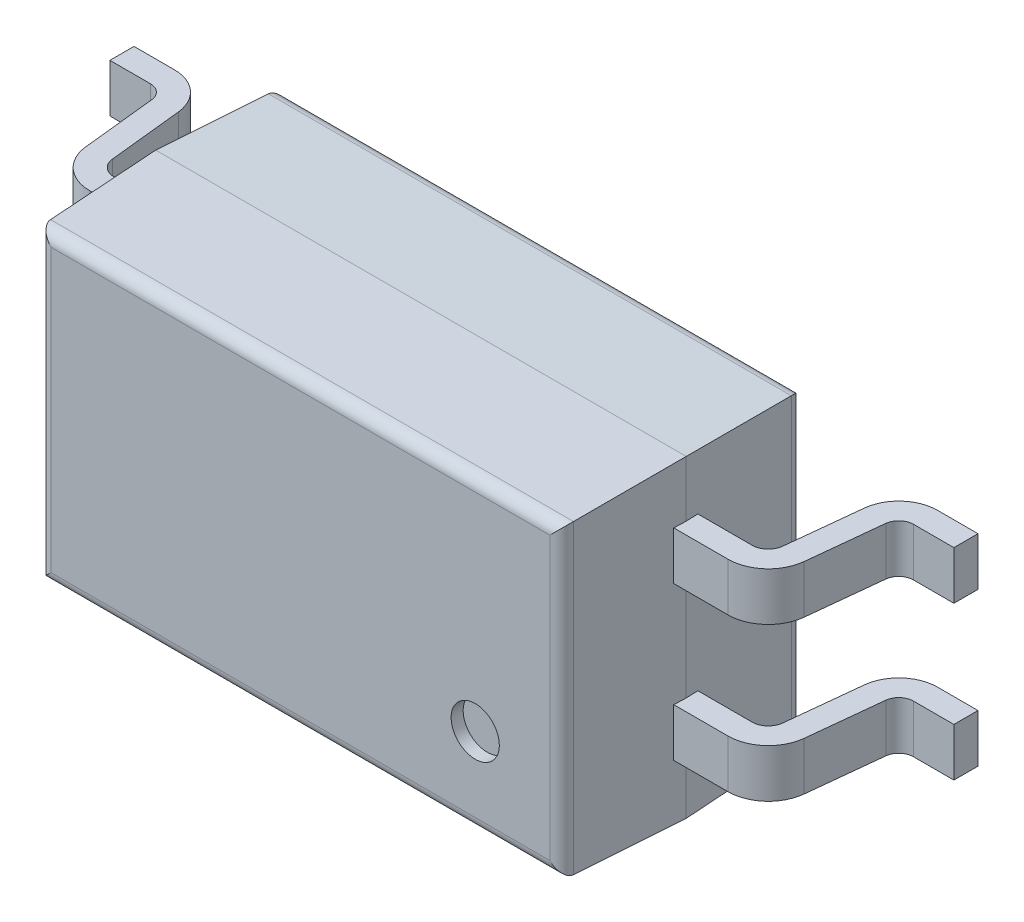
SolidWorks part; units mm, degrees
ref_plane "Plan de face" through (0, 0, 0) normal (0, 0, 1) x (1, 0, 0)
ref_plane "Plan de dessus" through (0, 0, 0) normal (0, 1, 0) x (1, 0, 0)
ref_plane "Plan de droite" through (0, 0, 0) normal (1, 0, 0) x (0, 0, -1)
sketch "Esquisse1" plane through (0, 0, 0) normal (0, 0, 1) x (1, 0, 0)
  line L1 (4.4, 2.6) -> (0, 2.6)
  line L2 (4.4, 2.6) -> (4.4, 0)
  line L3 (4.4, 0) -> (0, 0)
  line L4 (0, 2.6) -> (0, 0)
  dimension "D1" = 2.6
  dimension "D2" = 4.4
extrude "Boss.-Extru.1" add sketch "Esquisse1" along normal blind 2
chamfer "Chanfrein1" distance 1 angle 2 4 edges at (2.2, 0, 2) (0, 1.3, 2) (4.4, 1.3, 2) (2.2, 2.6, 2) first distance on face at (2.2, 0, 1) first distance on face at (0, 1.3, 1) first distance on face at (4.4, 1.3, 1) first distance on face at (2.2, 2.6, 1)
chamfer "Chanfrein2" distance 1 angle 2 4 edges at (2.2, 0, 0) (4.4, 1.3, 0) (2.2, 2.6, 0) (0, 1.3, 0) first distance on face at (2.2, 0, 0.5) first distance on face at (4.4, 1.3, 0.5) first distance on face at (2.2, 2.6, 0.5) first distance on face at (0, 1.3, 0.5)
sketch "Esquisse2" plane through (0, 0, 2) normal (0, 0, 1) x (1, 0, 0)
  line L0 (4.4, 2.6) -> (4.4, 0) construction
  line L1 (4.4, 0) -> (0, 0) construction
  circle A0 centre (3.65, 0.75) radius 0.2
  dimension "D1" = 0.4
  dimension "D2" = 0.75
  dimension "D3" = 0.75
extrude "Enlèv. mat.-Extru.1" cut sketch "Esquisse2" against normal blind 0.1
sketch "Esquisse3" plane through (0, 0, 2) normal (0, 0, 1) x (1, 0, 0)
  line L0 (4.4, 2.6) -> (4.737, 2.6) construction
  line L1 (4.6992, 2.0715) -> (4.3992, 2.0715)
  line L2 (4.6992, 2.0715) -> (4.6992, 1.7715)
  line L3 (4.6992, 1.7715) -> (4.3992, 1.7715)
  line L4 (4.3992, 2.0715) -> (4.3992, 1.7715)
  line L5 (-0.2996, 2.0715) -> (0.0004, 2.0715)
  line L6 (-0.2996, 2.0715) -> (-0.2996, 1.7715)
  line L7 (-0.2996, 1.7715) -> (0.0004, 1.7715)
  line L8 (0.0004, 2.0715) -> (0.0004, 1.7715)
  line L9 (4.737, 2.6) -> (4.737, 2.1691) construction
  line L10 (4.737, 2.1691) -> (4.737, 1.935) construction
  line L11 (4.737, 0.8991) -> (4.737, 0.665) construction
  line L12 (4.737, 0.665) -> (4.737, 0.4309) construction
  line L13 (4.737, 0.4309) -> (4.737, 0) construction
  line L14 (4.4, 0) -> (4.737, 0) construction
  line L16 (4.737, 1.935) -> (4.737, 1.7009) construction
  line L17 (4.737, 1.7009) -> (4.737, 0.8991) construction
  line L18 (4.4, 1.3) -> (4.737, 1.3) construction
  line L19 (4.4, 2.6) -> (4.4, 0) construction
  dimension "D1" = 0.3
  dimension "D2" = 0.3
  dimension "D3" = 0.3
  dimension "D4" = 0.3
  dimension "D5" = 1.27
extrude "Enlèv. mat.-Extru.2" cut sketch "Esquisse3" against normal through all
sketch "Esquisse4" plane through (4.3992, 0, 0) normal (1, 0, 0) x (0, 0, -1)
  line L0 (-1.1, 2.135) -> (-1, 2.135)
  line L1 (-1, 2.6) -> (-1, 2.0715) construction
  line L2 (-1.1, 2.135) -> (-1.1, 1.735)
  line L3 (-1.1, 1.735) -> (-0.9, 1.735)
  line L4 (-0.9, 2.135) -> (-0.9, 1.735)
  line L5 (-1.1, 0.865) -> (-0.9, 0.865)
  line L6 (-1.1, 0.865) -> (-1.1, 0.465)
  line L7 (-1.1, 0.465) -> (-0.9, 0.465)
  line L8 (-0.9, 0.865) -> (-0.9, 0.465)
  line L9 (-1, 2.135) -> (-0.9, 2.135)
  line L10 (-1.1, 1.735) -> (-1.1, 1.3) construction
  line L11 (-1.1, 1.3) -> (-1.1, 0.865) construction
  line L12 (-2, 1.3) -> (-1.1, 1.3) construction
  line L13 (-2, 0.0349) -> (-2, 2.5651) construction
  line L14 (-1.1, 0.865) -> (-0.9, 0.465) construction
  line L15 (-1.1, 1.735) -> (-0.9, 2.135) construction
  line L16 (-1.1, 2.135) -> (-1, 1.935) construction
  line L17 (-1.1, 0.465) -> (-1, 0.665) construction
  dimension "D1" = 0.4
  dimension "D2" = 0.2
  dimension "D3" = 1.27
extrude "Boss.-Extru.2" add sketch "Esquisse4" along normal up to vertex (0.0008 mm away) and the other way up to vertex (4.3992 mm away) up to point (4.4, 0, 1) other way up to point (0, 0, 1)
sketch "Esquisse5" plane through (0, 0, 0) normal (-1, 0, 0) x (0, 0, 1)
  line L0 (1.1, 1.735) -> (1, 1.735) construction
  line L1 (1.1, 0.465) -> (-0.12, 0.465)
  line L2 (1.1, 0.465) -> (1.1, 0.865)
  line L3 (1.1, 0.865) -> (-0.12, 0.865)
  line L4 (-0.12, 0.465) -> (-0.12, 0.865)
  line L5 (1.1, 1.735) -> (-0.12, 1.735)
  line L6 (1.1, 1.735) -> (1.1, 2.135)
  line L7 (1.1, 2.135) -> (-0.12, 2.135)
  line L8 (-0.12, 1.735) -> (-0.12, 2.135)
  line L9 (1.1, 2.135) -> (1.1, 1.735) construction
  line L10 (1, 2.135) -> (1.1, 2.135) construction
  line L11 (0.9, 0.865) -> (1, 0.865) construction
  line L12 (0, 0.0349) -> (0, 2.5651) construction
  dimension "D1" = 0.12
extrude "Boss.-Extru.3" add sketch "Esquisse5" along normal blind 1.3
sketch "Esquisse6" plane through (4.4, 0, 0) normal (1, 0, 0) x (0, 0, -1)
  line L1 (-1.1, 2.135) -> (0.12, 2.135)
  line L2 (-1.1, 2.135) -> (-1.1, 1.735)
  line L3 (-1.1, 1.735) -> (0.12, 1.735)
  line L4 (0.12, 2.135) -> (0.12, 1.735)
  line L5 (-1.1, 0.865) -> (0.12, 0.865)
  line L6 (-1.1, 0.865) -> (-1.1, 0.465)
  line L7 (-1.1, 0.465) -> (0.12, 0.465)
  line L8 (0.12, 0.865) -> (0.12, 0.465)
extrude "Boss.-Extru.4" add sketch "Esquisse6" along normal blind 1.3
sketch "Esquisse7" plane through (0, 0.465, 0) normal (0, -1, 0) x (1, 0, 0)
  line L0 (2.2, 0) -> (2.2, 2) construction
  line L1 (4.3651, 0) -> (0.0349, 0) construction
  line L2 (0.0349, 2) -> (4.3651, 2) construction
  line L3 (0, 0.9) -> (-0.4465, 0.9)
  line L4 (-1.3, 0.08) -> (-0.9642, 0.08)
  line L5 (-1.3, -0.12) -> (-1.3, 1.1) construction
  line L6 (-1.3, -0.12) -> (0, -0.12) construction
  line L7 (0.0035, 1.1) -> (-1.3, 1.1) construction
  line L8 (-0.5799, 0.78) -> (-0.6448, 0.1674)
  line L9 (-0.7788, 0.801) -> (-0.8437, 0.1885)
  line L10 (-1.3, 0.08) -> (-1.3, 1.1)
  line L11 (-1.3, 1.1) -> (-0.4465, 1.1)
  line L12 (0, 0.9) -> (0, -0.12)
  line L13 (0, -0.12) -> (-0.9642, -0.12)
  line L14 (-0.7788, 0.801) -> (-0.5799, 0.78) construction
  line L15 (-0.8437, 0.1885) -> (-0.6448, 0.1674) construction
  line L16 (5.2437, 0.1885) -> (5.0448, 0.1674) construction
  line L17 (5.1788, 0.801) -> (4.9799, 0.78) construction
  line L18 (4.4, -0.12) -> (5.3642, -0.12)
  line L19 (4.4, 0.9) -> (4.4, -0.12)
  line L20 (5.7, 1.1) -> (4.8465, 1.1)
  line L21 (5.7, 0.08) -> (5.7, 1.1)
  line L22 (5.1788, 0.801) -> (5.2437, 0.1885)
  line L23 (4.9799, 0.78) -> (5.0448, 0.1674)
  line L24 (5.7, 0.08) -> (5.3642, 0.08)
  line L25 (4.4, 0.9) -> (4.8465, 0.9)
  arc A0 (-0.4465, 1.1) -> (-0.7788, 0.801) centre (-0.4465, 0.7658) ccw
  arc A1 (-0.4465, 0.9) -> (-0.5799, 0.78) centre (-0.4465, 0.7658) ccw
  arc A2 (-0.8437, 0.1885) -> (-0.9642, 0.08) centre (-0.9642, 0.2012) cw
  arc A3 (-0.6448, 0.1674) -> (-0.9642, -0.12) centre (-0.9642, 0.2012) cw
  arc A4 (5.0448, 0.1674) -> (5.3642, -0.12) centre (5.3642, 0.2012) ccw
  arc A5 (5.2437, 0.1885) -> (5.3642, 0.08) centre (5.3642, 0.2012) ccw
  arc A6 (4.8465, 0.9) -> (4.9799, 0.78) centre (4.8465, 0.7658) cw
  arc A7 (4.8465, 1.1) -> (5.1788, 0.801) centre (4.8465, 0.7658) cw
  dimension "D1" = 0.2
  dimension "D2" = 0.45
  dimension "D3" = 0.2
extrude "Enlèv. mat.-Extru.3" cut sketch "Esquisse7" against normal through all
fillet "Congé1" radius 0.1 4 edges at (4.3651, 1.3, 2) (2.2, 0.0349, 2) (0.0349, 1.3, 2) (2.2, 2.5651, 2)
fillet "Congé2" radius 0.1 4 edges at (4.3651, 1.3, 0) (2.2, 2.5651, 0) (0.0349, 1.3, 0) (2.2, 0.0349, 0)
ref_plane "Plane1" through (0, 1.3, 0) normal (0, -1, 0) x (-1, 0, 0)
ref_plane "Plane2" through (2.2, 0, 0) normal (-1, 0, 0) x (0, 0, 1)
ref_plane "Plane4" through (0, 0, -0.12) normal (0, 0, -1) x (-1, 0, 0)
